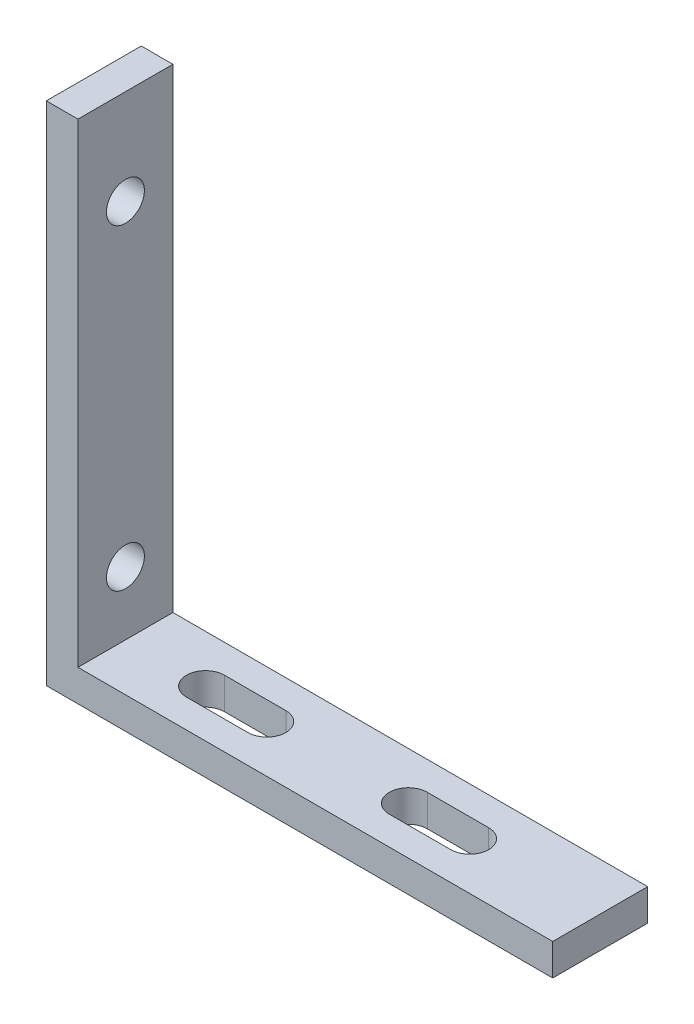
SolidWorks part; units mm, degrees
ref_plane "Front Plane" through (0, 0, 0) normal (0, 0, 1) x (1, 0, 0)
ref_plane "Top Plane" through (0, 0, 0) normal (0, 1, 0) x (1, 0, 0)
ref_plane "Right Plane" through (0, 0, 0) normal (1, 0, 0) x (0, 0, -1)
sketch "Sketch1" plane through (0, 0, 0) normal (0, 1, 0) x (1, 0, 0)
  line L1 (-30.1722, 4.0464) -> (49.8278, 4.0464)
  line L2 (-30.1722, 4.0464) -> (-30.1722, -10.9536)
  line L3 (-30.1722, -10.9536) -> (49.8278, -10.9536)
  line L4 (49.8278, 4.0464) -> (49.8278, -10.9536)
  dimension "D1" = 15
  dimension "D2" = 80
extrude "Boss-Extrude1" add sketch "Sketch1" along normal blind 5
sketch "Sketch3" plane through (0, 5, 0) normal (0, 1, 0) x (1, 0, 0)
  line L0 (-30.1722, 4.0464) -> (-25.1722, 4.0464)
  line L1 (49.8278, 4.0464) -> (-30.1722, 4.0464) construction
  line L2 (-30.1722, -10.9536) -> (-25.1722, -10.9536)
  line L3 (-30.1722, -10.9536) -> (49.8278, -10.9536) construction
  line L4 (-25.1722, 4.0464) -> (-25.1722, -10.9536)
  line L5 (-30.1722, 4.0464) -> (-30.1722, -10.9536)
extrude "Boss-Extrude2" add sketch "Sketch3" along normal blind 75
sketch "Sketch4" plane through (-30.1722, 0, 0) normal (-1, 0, 0) x (0, 0, 1)
  line L0 (3.4536, 80) -> (3.4536, 0)
  line L1 (-4.0464, 80) -> (10.9536, 80) construction
  line L2 (-4.0464, 0) -> (10.9536, 0) construction
  line L3 (3.4536, 0) -> (3.4536, 15)
  line L4 (3.4536, 80) -> (3.4536, 65)
hole_wizard "Ø6.0mm Dowel Hole1" positions "Sketch5" profile "Sketch6" hole size "Ø6.0" standard "ANSI Metric" end condition up to next
sketch "Sketch5" plane through (-30.1722, 0, 0) normal (-1, 0, 0) x (0, 0, 1)
  point P0 (3.4536, 65)
  point P3 (3.4536, 15)
sketch "Sketch6" plane through (-30.1722, 65, 3.4536) normal (0, 1, 0) x (0, 0, 1)
  line L0 (0, 0) -> (0, 5)
  line L1 (0, 5) -> (3, 5)
  line L2 (3, 5) -> (3, 0)
  line L5 (3, 0) -> (0, 0)
  line L11 (0, -6.35) -> (0, 107.95) construction
  dimension "Thru Hole Dia." = 6
  dimension "Thru Hole Depth" = 5
sketch "Sketch7" plane through (0, 0, 0) normal (0, -1, 0) x (1, 0, 0)
  line L0 (-30.1722, 3.4536) -> (49.8278, 3.4536)
  line L1 (-30.1722, -4.0464) -> (-30.1722, 10.9536) construction
  line L2 (49.8278, 10.9536) -> (49.8278, -4.0464) construction
hole_wizard "Ø6.0mm Dowel Slot1" positions "Sketch8" profile "Sketch9" size "Ø6.0" standard "ANSI Metric" slot yes end condition up to next
sketch "Sketch8" plane through (0, 5, 0) normal (0, 1, 0) x (1, 0, 0)
  line L0 (-15.5307, -3.4536) -> (0.1693, -3.4536) construction
  point P0 (-7.6807, -3.4536)
  point P5 (24.3593, -3.4534)
  point P9 (0, 0)
  point P10 (0, 0)
  dimension "D1" = 15.7
sketch "Sketch9" plane through (-7.6807, 5, 3.4536) normal (1, 0, 0) x (0, 0, 1)
  line L0 (0, 0) -> (0, 5)
  line L1 (0, 5) -> (3, 5)
  line L2 (3, 5) -> (3, 0)
  line L5 (3, 0) -> (0, 0)
  line L11 (0, -6.35) -> (0, 107.95) construction
  dimension "Thru Hole Dia." = 6
  dimension "Thru Hole Depth" = 5
